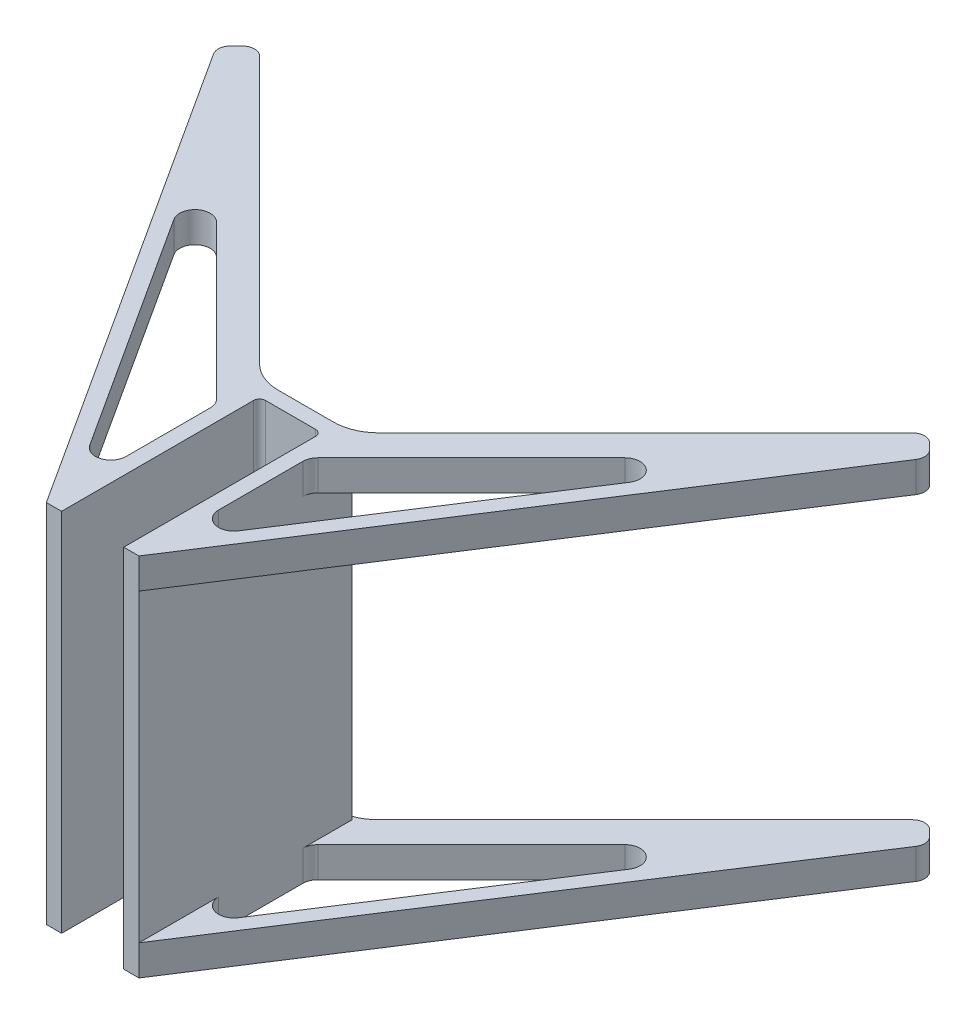
SolidWorks part; units mm, degrees
ref_plane "Front Plane" through (0, 0, 0) normal (0, 0, 1) x (1, 0, 0)
ref_plane "Top Plane" through (0, 0, 0) normal (0, 1, 0) x (1, 0, 0)
ref_plane "Right Plane" through (0, 0, 0) normal (1, 0, 0) x (0, 0, -1)
sketch "Sketch1" plane through (0, 0, 0) normal (0, 1, 0) x (1, 0, 0)
  line L0 (-117.0711, 92.7289) -> (-15.2, -65)
  line L1 (-10.2, 0) -> (10.2, 0)
  line L2 (-10.2, 0) -> (-10.2, -20.4)
  line L4 (10.2, 0) -> (10.2, -20.4)
  line L5 (-15.2, -65) -> (-15.2, 5)
  line L6 (-15.2, 5) -> (15.2, 5)
  line L7 (15.2, 5) -> (15.2, -65)
  line L8 (-100.2636, 75.9214) -> (-15.2, -55.7841)
  line L9 (-15.2, 5) -> (-110, 99.8)
  line L10 (-110, 99.8) -> (-117.0711, 92.7289)
  line L11 (-117.0711, 92.7289) -> (-15.2, -9.1421)
  line L12 (15.2, 5) -> (110, 99.8)
  line L13 (110, 99.8) -> (117.0711, 92.7289)
  line L14 (117.0711, 92.7289) -> (15.2, -9.1421)
  line L15 (-100, 89.8) -> (100, 89.8) construction
  line L16 (117.0711, 92.7289) -> (15.2, -65)
  line L17 (15.2, -55.7841) -> (100.2636, 75.9214)
  line L18 (-15.2, -65) -> (-10.2, -65)
  line L23 (-10.2, -20.4) -> (-10.2, -65)
  line L28 (10.2, -20.4) -> (10.2, -65)
  line L29 (10.2, -65) -> (15.2, -65)
  point P19 (132.281, 114.7746)
  dimension "D1" = 20.4
  dimension "D2" = 5
  dimension "D3" = 5
  dimension "D4" = 5
  dimension "D5" = 10
  dimension "D6" = 10
  dimension "D7" = 200
  dimension "D8" = 220
  dimension "D9" = 5
  dimension "D10" = 5
  dimension "D11" = 70
  dimension "D12" = 135
extrude "Boss-Extrude1" add sketch "Sketch1" along normal blind 120 contours L5 L18 L7 L6 L1 L4 L2 region at (-14.4368, 0, 60.3921)
extrude "Boss-Extrude2" add sketch "Sketch1<3>" along normal blind 10 contours L10 L11 L5 L9 | L14 L13 L12 L7 | L17 L7 L16 L14 | L11 L0 L5 L8 region at (-62.0596, 0, -12.0234) region at (-64.389, 0, -47.0331) region at (64.389, 0, -47.0331) region at (62.0596, 0, -12.0234)
sketch "Sketch1<3>" plane through (0, 0, 0) normal (0, 1, 0) x (1, 0, 0) same geometry as "Sketch1"
extrude "Boss-Extrude3" add sketch "Sketch1<4>" against normal blind 10 from surface contours L10 L11 L5 L9 | L11 L0 L5 L8 | L14 L13 L12 L7 | L17 L7 L16 L14 region at (-62.0596, 0, -12.0234) region at (-64.389, 0, -47.0331) region at (64.389, 0, -47.0331) region at (62.0596, 0, -12.0234) starting at face at (0, 120, 31.25)
sketch "Sketch1<4>" plane through (0, 0, 0) normal (0, 1, 0) x (1, 0, 0) same geometry as "Sketch1"
fillet "Fillet1" radius 5 12 edges at (-100.2636, 115, -75.9214) (-15.2, 115, 55.7841) (-15.2, 115, 9.1421) (-100.2636, 5, -75.9214) (-15.2, 5, 55.7841) (-15.2, 5, 9.1421) (100.2636, 115, -75.9214) (15.2, 115, 55.7841) (15.2, 115, 9.1421) (100.2636, 5, -75.9214) (15.2, 5, 55.7841) (15.2, 5, 9.1421)
fillet "Fillet2" radius 15 4 edges at (-15.2, 5, -5) (15.2, 5, -5) (-15.2, 115, -5) (15.2, 115, -5)
fillet "Fillet3" radius 2 2 edges at (-10.2, 60, 0) (10.2, 60, 0)
fillet "Fillet4" radius 4 8 edges at (117.0711, 115, -92.7289) (110, 115, -99.8) (117.0711, 5, -92.7289) (110, 5, -99.8) (-117.0711, 115, -92.7289) (-110, 115, -99.8) (-117.0711, 5, -92.7289) (-110, 5, -99.8)
